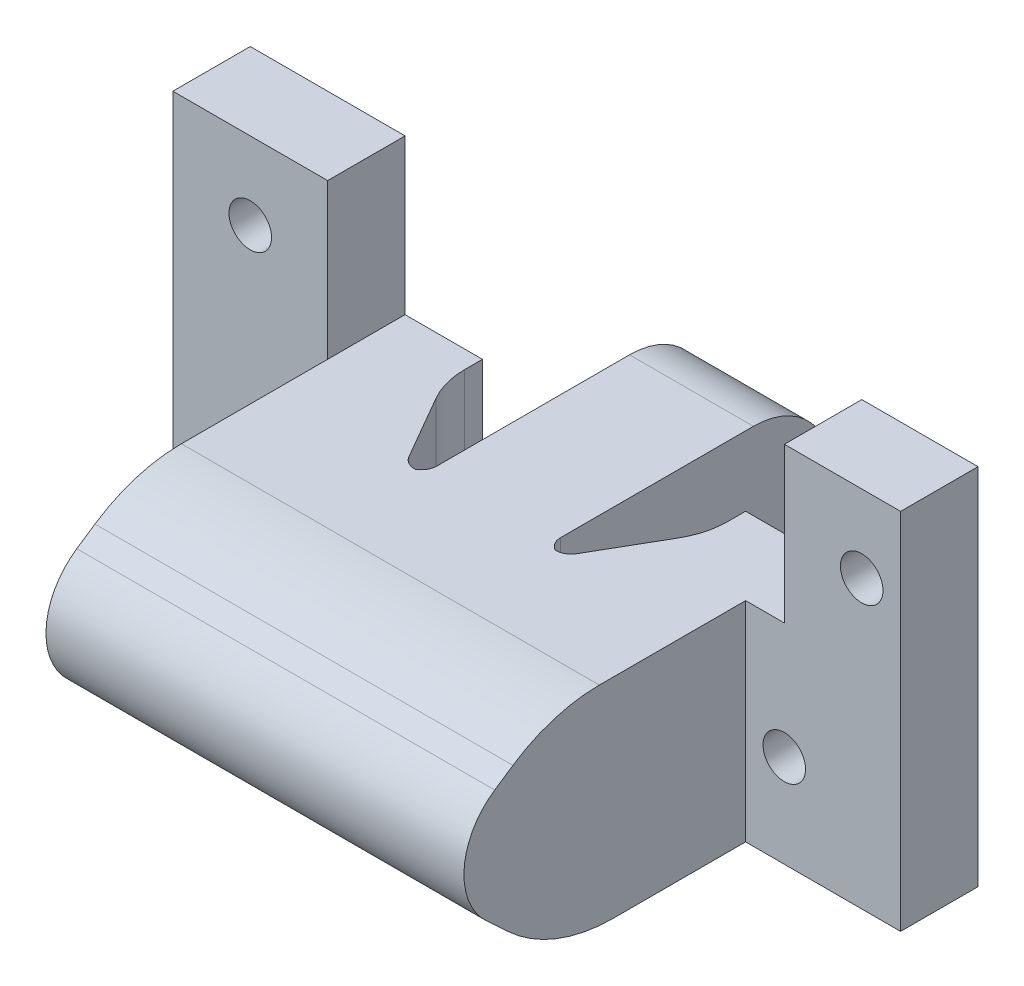
SolidWorks part; units mm, degrees
ref_plane "Front Plane" through (0, 0, 0) normal (0, 0, 1) x (1, 0, 0)
ref_plane "Top Plane" through (0, 0, 0) normal (0, 1, 0) x (1, 0, 0)
ref_plane "Right Plane" through (0, 0, 0) normal (1, 0, 0) x (0, 0, -1)
sketch "Sketch2" plane through (0, 0, 0) normal (0, 0, 1) x (1, 0, 0)
  line L6 (44, -75) -> (44, -102)
  line L7 (44, -102) -> (74.0263, -102)
  line L8 (74.0263, -102) -> (74.0263, -55)
  line L9 (74.0263, -55) -> (59.0132, -55)
  line L10 (59.0132, -55) -> (59, -75)
  line L11 (59, -75) -> (44, -75)
  line L12 (44, -75) -> (44, -102)
  line L13 (44, -102) -> (74.0263, -102)
  line L14 (74.0263, -102) -> (74.0263, -55)
  line L15 (74.0263, -55) -> (59.0132, -55)
  line L16 (59.0132, -55) -> (59, -75)
  line L17 (59, -75) -> (44, -75)
  line L18 (-20, -55) -> (-20, -102)
  line L19 (-20, -102) -> (10, -102)
  line L20 (10, -102) -> (10, -75)
  line L21 (10, -75) -> (0, -75)
  line L22 (0, -75) -> (0, -55)
  line L23 (0, -55) -> (-20, -55)
  line L24 (-20, -55) -> (-20, -102)
  line L25 (-20, -102) -> (10, -102)
  line L26 (10, -102) -> (10, -75)
  line L27 (10, -75) -> (0, -75)
  line L28 (0, -75) -> (0, -55)
  line L29 (0, -55) -> (-20, -55)
  circle A0 centre (-10, -65) radius 2.75 construction
  circle A1 centre (-5, -90) radius 2.75 construction
  circle A2 centre (59, -90) radius 2.75 construction
  circle A3 centre (69, -65) radius 2.75 construction
  circle A4 centre (-10, -65) radius 2.75
  circle A5 centre (-5, -90) radius 2.75
  circle A6 centre (59, -90) radius 2.75
  circle A7 centre (69, -65) radius 2.75
  dimension "D1" = 0
  dimension "D2" = 0
extrude "Boss-Extrude1" add sketch "Sketch2" along normal blind 10
sketch "Sketch3" plane through (0, 0, 10) normal (0, 0, 1) x (1, 0, 0)
  line L0 (44, -102) -> (10, -102)
  line L1 (0, -75) -> (10, -75)
  line L2 (0, -75) -> (0, -102)
  line L3 (0, -102) -> (10, -102)
  line L4 (10, -75) -> (10, -102)
  line L11 (27, -102) -> (27, -98.4961)
  line L12 (44, -75) -> (44, -102)
  line L13 (54, -102) -> (44, -102)
  line L14 (54, -75) -> (54, -102)
  line L15 (54, -75) -> (44, -75)
  line M6 (-20, -102) -> (10, -102)
  line M7 (10, -102) -> (10, -75)
  line M8 (10, -75) -> (0, -75)
extrude "Boss-Extrude2" add sketch "Sketch3" along normal blind 15 contours L2 M8 M6 M7 | L14 L15 L12 L13 region at (5, -88.5, 10) region at (49, -88.5, 10)
sketch "Sketch4" plane through (0, 0, 25) normal (0, 0, 1) x (1, 0, 0)
  line L1 (0, -75) -> (54, -75)
  line L2 (0, -75) -> (0, -102)
  line L3 (0, -102) -> (54, -102)
  line L4 (54, -75) -> (54, -102)
extrude "Boss-Extrude3" add sketch "Sketch4" along normal blind 10
chamfer "Chamfer1" distance 20 angle 30 2 edges at (10, -88.5, 25) (44, -88.5, 25) first distance on face at (10, -88.5, 12.5) first distance on face at (44, -88.5, 12.5)
fillet "Fillet1" radius 10 4 edges at (44, -88.5, 5) (10, -88.5, 5) (21.547, -88.5, 25) (32.453, -88.5, 25)
sketch "Sketch5" plane through (0, 0, 0) normal (-1, 0, 0) x (0, 0, 1)
  line L0 (43.5333, -94.0328) -> (35, -102)
  line L1 (42.414, -79.9863) -> (35, -75)
  line L2 (35, -75) -> (10, -75) construction
  line L3 (35, -75) -> (35, -102) construction
  line L4 (35, -75) -> (35, -102)
  circle A0 centre (37.3913, -87.4544) radius 9
  line M5 (35, -102) -> (35, -75)
  dimension "D1" = 18
extrude "Boss-Extrude4" add sketch "Sketch5" against normal up to surface (54 mm away) contours A0 L1 M5 | A0 L4 | A0 L0 M5 region at (0, -87.4544, 39.9563) region at (0, -98.0808, 37.2732) region at (0, -77.4431, 36.9284) up to face at (54, -88.5, 22.5)
fillet "Fillet2" radius 20 2 edges at (27, -102, 35) (27, -75, 35)
sketch "Sketch6" plane through (0, -102, 0) normal (0, -1, 0) x (1, 0, 0)
  line L0 (27, 24.9949) -> (27, -20.0051)
  line L1 (19, 24.9949) -> (19, -20.0051)
  line L2 (35, 24.9949) -> (35, -20.0051)
  line L3 (19, 24.9949) -> (35, 24.9949)
  line L4 (19, -20.0051) -> (35, -20.0051)
  arc M11 (18.6603, 20) -> (27, 24.9949) centre (27.3205, 15) cw
  arc M12 (27, 24.9949) -> (35.3397, 20) centre (26.6795, 15) cw
  dimension "D1" = 45
  dimension "D2" = 8
  dimension "D3" = 8
extrude "Boss-Extrude5" add sketch "Sketch6" against normal up to surface (27 mm away) contours L1 L4 L0 M11 | L0 L4 L2 M12 region at (30.9363, -102, 1.8288) region at (23.0637, -102, 1.8288) up to face at (29.3125, -75, 10.901)
fillet "Fillet3" radius 10 2 edges at (27, -75, -20.0051) (27, -102, -20.0051)
sketch "Sketch7" plane through (0, -102, 0) normal (0, -1, 0) x (1, 0, 0)
  circle A0 centre (35, 20.547) radius 4
  circle A1 centre (19, 20.547) radius 4
  dimension "D1" = 8
  dimension "D2" = 8
extrude "Boss-Extrude6" add sketch "Sketch7" against normal up to surface (27 mm away) up to face at (28.9474, -75, 8.8604)
fillet "Fillet4" radius 2 4 edges at (19, -88.5, 16.547) (16.9821, -88.5, 17.0933) (37.0179, -88.5, 17.0933) (35, -88.5, 16.547)
